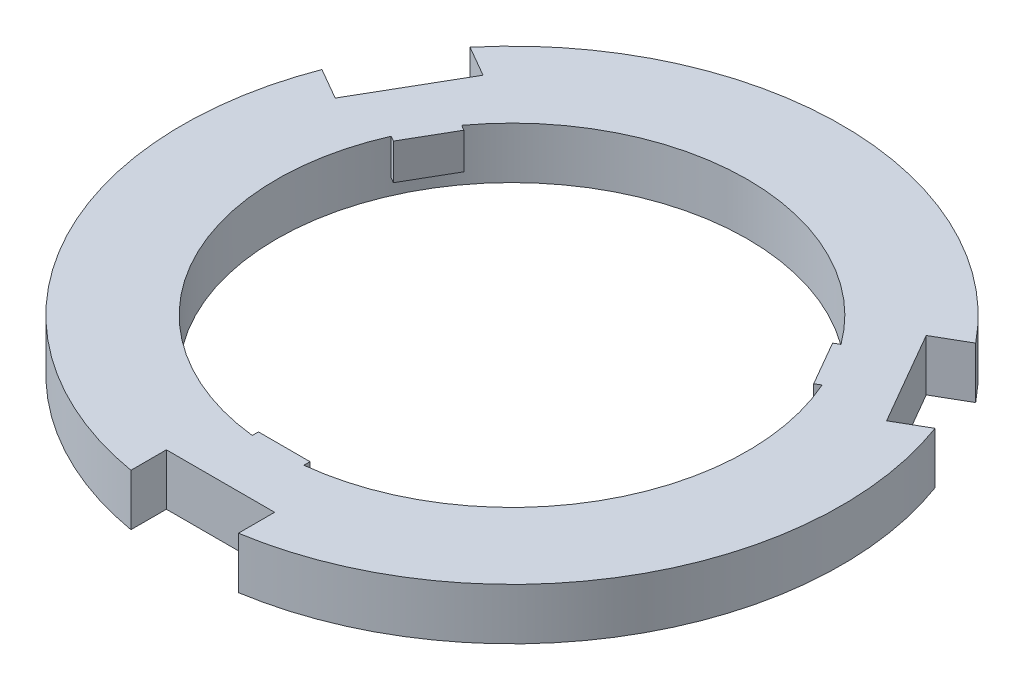
SolidWorks part; units mm, degrees
ref_plane "Front Plane" through (0, 0, 0) normal (0, 0, 1) x (1, 0, 0)
ref_plane "Top Plane" through (0, 0, 0) normal (0, 1, 0) x (1, 0, 0)
ref_plane "Right Plane" through (0, 0, 0) normal (1, 0, 0) x (0, 0, -1)
sketch "Sketch2" plane through (0, 0, 0) normal (0, 1, 0) x (1, 0, 0)
  line L0 (0, 0) -> (0, -30.7533) construction
  line L1 (-5.4665, -28.0858) -> (-5.4665, -31.5296)
  line L6 (5.0405, -28.0858) -> (5.0405, -31.6005)
  line L7 (-26.8433, 9.6777) -> (-29.8871, 11.435)
  line L8 (-5.4665, -28.0858) -> (5.0405, -28.0858)
  line L9 (-21.5898, 18.777) -> (-26.8433, 9.6777)
  line L10 (-21.5898, 18.777) -> (-24.5722, 20.4989)
  line L11 (21.8028, 18.4082) -> (24.8466, 20.1655)
  line L12 (27.0563, 9.3088) -> (21.8028, 18.4082)
  line L13 (27.0563, 9.3088) -> (30.0387, 11.0307)
  line L14 (-2.5026, -22.1121) -> (2.5026, -22.1121)
  line L15 (2.5026, -22.1121) -> (2.5026, -22.7121)
  line L16 (-2.5026, -22.1121) -> (-2.5026, -22.7121)
  line L17 (-20.4009, 8.8887) -> (-20.9205, 9.1887)
  line L18 (-17.8983, 13.2233) -> (-20.4009, 8.8887)
  line L19 (-17.8983, 13.2233) -> (-18.4179, 13.5233)
  line L20 (17.8983, 13.2233) -> (18.4179, 13.5233)
  line L21 (20.4009, 8.8887) -> (17.8983, 13.2233)
  line L22 (20.4009, 8.8887) -> (20.9205, 9.1887)
  arc A2 (-5.4665, -31.5296) -> (5.0405, -31.6005) centre (0, 0) ccw
  arc A3 (-24.5722, 20.4989) -> (-29.8871, 11.435) centre (0, 0) ccw
  arc A4 (30.0387, 11.0307) -> (24.8466, 20.1655) centre (0, 0) ccw
  arc A5 (-29.8871, 11.435) -> (-5.4665, -31.5296) centre (0, 0) ccw
  arc A6 (24.8466, 20.1655) -> (-24.5722, 20.4989) centre (0, 0) ccw
  arc A7 (5.0405, -31.6005) -> (30.0387, 11.0307) centre (0, 0) ccw
  arc A11 (-20.9205, 9.1887) -> (-2.5026, -22.7121) centre (0, 0) ccw
  arc A12 (2.5026, -22.7121) -> (20.9205, 9.1887) centre (0, 0) ccw
  arc A13 (18.4179, 13.5233) -> (-18.4179, 13.5233) centre (0, 0) ccw
  circle A14 centre (0, 0) radius 22.8495
  point P25 (0, -22.1121)
  dimension "D1" = 10.507
  dimension "D3" = 3
  dimension "D4" = 0.6
  dimension "D2" = 3
extrude "Boss-Extrude4" add sketch "Sketch2" along normal blind 3 contours A13 L20 L21 L22 A12 L15 L14 L8 L6 A7 L13 L12 L11 A6 L10 L9 L7 A5 L1 L16 A11 L17 L18 L19 region at (-6.3688, 0, 29.8077)
extrude "Boss-Extrude5" add sketch "Sketch2<12>" against normal blind 2 contours A14 A12 L8 L6 A7 L13 L12 L11 A6 L10 L9 L7 A5 L1 A11 A13 region at (-6.3688, 0, 29.8077)
sketch "Sketch2<12>" plane through (0, 0, 0) normal (0, 1, 0) x (1, 0, 0) same geometry as "Sketch2"
extrude "Boss-Extrude6" add sketch "Sketch2<13>" along normal blind 3 and the other way blind 0.5 contours L19 A14 L17 L18 | L22 A14 L20 L21 | L14 L0 A14 L15 | L0 L14 L16 A14 region at (1.2099, 0, 22.4591) region at (-1.2099, 0, 22.4591) region at (-19.4502, 0, -11.2296) region at (19.4502, 0, -11.2296)
sketch "Sketch2<13>" plane through (0, 0, 0) normal (0, 1, 0) x (1, 0, 0) same geometry as "Sketch2"
